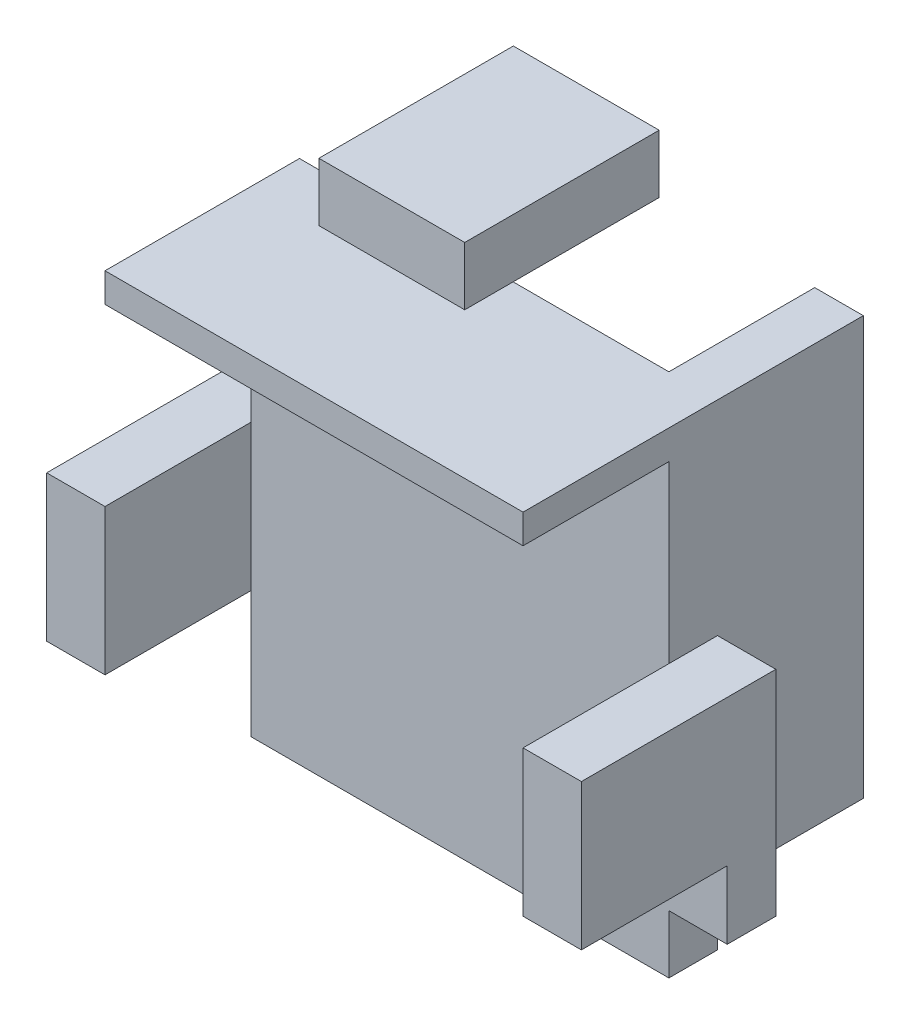
SolidWorks part; units mm, degrees
material "ABS"
ref_plane "前视基准面" through (0, 0, 0) normal (0, 0, 1) x (1, 0, 0)
ref_plane "上视基准面" through (0, 0, 0) normal (0, 1, 0) x (1, 0, 0)
ref_plane "右视基准面" through (0, 0, 0) normal (1, 0, 0) x (0, 0, -1)
sketch "草图1" plane through (0, 0, 0) normal (0, 0, 1) x (1, 0, 0)
  line L0 (-50.797, 9.0326) -> (-50.797, 3.0326)
  line L1 (-77.797, 31.0326) -> (-71.797, 31.0326)
  line L2 (-77.797, 31.0326) -> (-77.797, 9.0326)
  line L3 (-77.797, 9.0326) -> (-50.797, 9.0326)
  line L4 (-22.797, 31.0326) -> (-22.797, 9.0326)
  line L5 (-50.797, 58.0326) -> (-28.797, 58.0326)
  line L6 (-50.797, 58.0326) -> (-50.797, 52.0326)
  line L7 (-50.797, 3.0326) -> (-28.797, 3.0326)
  line L8 (-28.797, 58.0326) -> (-28.797, 31.0326)
  line L9 (-28.797, 9.0326) -> (-28.797, 3.0326)
  line L10 (-28.797, 9.0326) -> (-22.797, 9.0326)
  line L11 (-28.797, 31.0326) -> (-22.797, 31.0326)
  line L12 (-50.797, 49.0326) -> (-50.797, 31.0326)
  line L13 (-50.797, 9.0326) -> (-35.797, 9.0326)
  line L14 (-50.797, 9.0326) -> (-50.797, 3.0326)
  line L15 (-50.797, 3.0326) -> (-35.797, 3.0326)
  line L16 (-35.797, 9.0326) -> (-35.797, 3.0326)
  line L17 (-50.797, 52.0326) -> (-35.797, 52.0326)
  line L18 (-50.797, 52.0326) -> (-50.797, 58.0326)
  line L19 (-50.797, 58.0326) -> (-35.797, 58.0326)
  line L20 (-35.797, 52.0326) -> (-35.797, 58.0326)
  line L21 (-28.797, 31.0326) -> (-22.797, 31.0326)
  line L22 (-28.797, 31.0326) -> (-28.797, 16.0326)
  line L23 (-28.797, 16.0326) -> (-22.797, 16.0326)
  line L24 (-22.797, 31.0326) -> (-22.797, 16.0326)
  line L25 (-77.797, 31.0326) -> (-71.797, 31.0326)
  line L26 (-77.797, 31.0326) -> (-77.797, 16.0326)
  line L27 (-77.797, 16.0326) -> (-71.797, 16.0326)
  line L28 (-71.797, 31.0326) -> (-71.797, 16.0326)
  line L29 (-68.797, 9.0326) -> (-71.797, 9.0326)
  line L30 (-68.797, 9.0326) -> (-68.797, 49.0326)
  line L31 (-68.797, 49.0326) -> (-71.797, 49.0326)
  line L32 (-71.797, 9.0326) -> (-71.797, 49.0326)
  line L33 (-28.797, 49.0326) -> (-71.797, 49.0326)
  line L34 (-28.797, 49.0326) -> (-28.797, 52.0326)
  line L35 (-28.797, 52.0326) -> (-71.797, 52.0326)
  line L36 (-71.797, 49.0326) -> (-71.797, 52.0326)
  line L37 (-68.797, 31.0326) -> (-50.797, 31.0326)
  dimension "D1" = 55
  dimension "D2" = 22
  dimension "D3" = 55
  dimension "D4" = 22
  dimension "D5" = 6
  dimension "D6" = 6
  dimension "D7" = 15
  dimension "D8" = 6
  dimension "D9" = 15
  dimension "D10" = 15
  dimension "D11" = 6
  dimension "D12" = 15
  dimension "D13" = 3
  dimension "D14" = 40
extrude "拉伸-薄壁3" add sketch "草图1" along normal blind 15 thin contours L11 thin type one direction wall 15
extrude "凸台-拉伸3" add sketch "草图1<7>" along normal blind 15 separate body contours L28 L1 L2 L27 region at (-74.797, 23.5326, 0)
sketch "草图1<7>" plane through (0, 0, 0) normal (0, 0, 1) x (1, 0, 0) same geometry as "草图1"
extrude "凸台-拉伸4" add sketch "草图1<8>" along normal blind 15 separate body contours L36 L31 L33 L8 L35 L17 region at (-50.297, 50.5326, 0)
sketch "草图1<8>" plane through (0, 0, 0) normal (0, 0, 1) x (1, 0, 0) same geometry as "草图1"
extrude "凸台-拉伸5" add sketch "草图1<11>" against normal blind 5 contours L37 L30 L3 L13 L16 L7 L9 L10 L4 L23 L22 L8 L33 L12 | L30 L37 L12 L33 | L22 L23 L4 L11 | L28 L1 L2 L27 | L32 L3 L30 L31 L28 | L36 L31 L33 L8 L35 L17 | L17 L20 L5 L6 | L35 L8 L5 L20 | L16 L13 L0 L7 region at (-43.297, 6.0326, 0) region at (-44.9565, 25.1922, 0) region at (-70.297, 29.0326, 0) region at (-59.797, 40.0326, 0) region at (-74.797, 23.5326, 0) region at (-50.297, 50.5326, 0) region at (-25.797, 23.5326, 0) region at (-43.297, 55.0326, 0) region at (-32.297, 55.0326, 0)
sketch "草图1<11>" plane through (0, 0, 0) normal (0, 0, 1) x (1, 0, 0) same geometry as "草图1"
extrude "凸台-拉伸10" add sketch "草图1<13>" against normal blind 20 contours L32 L29 L30 L31
sketch "草图1<13>" plane through (0, 0, 0) normal (0, 0, 1) x (1, 0, 0) same geometry as "草图1"
sketch "草图3" plane through (0, 0, -5) normal (0, 0, -1) x (-1, 0, 0)
  line L0 (50.797, 58.0326) -> (28.797, 58.0326) construction
  line L1 (35.9279, 58.0326) -> (50.797, 58.0326)
  line L2 (35.9279, 58.0326) -> (35.9279, 52.0326)
  line L3 (35.9279, 52.0326) -> (50.797, 52.0326)
  line L4 (50.797, 58.0326) -> (50.797, 52.0326)
  line L5 (50.797, 3.0326) -> (28.797, 3.0326) construction
  line L6 (50.797, 9.0326) -> (35.9279, 9.0326)
  line L7 (50.797, 9.0326) -> (50.797, 3.0326)
  line L8 (50.797, 3.0326) -> (35.9279, 3.0326)
  line L9 (35.9279, 9.0326) -> (35.9279, 3.0326)
extrude "凸台-拉伸15" add sketch "草图3" along normal blind 15
sketch "草图4" plane through (0, 0, -5) normal (0, 0, -1) x (-1, 0, 0)
  line L2 (50.797, 52.0326) -> (28.797, 52.0326)
  line L3 (50.797, 52.0326) -> (50.797, 58.0326)
  line L4 (50.797, 58.0326) -> (28.797, 58.0326)
  line L5 (28.797, 52.0326) -> (28.797, 58.0326)
  line L6 (71.797, 52.0326) -> (64.797, 52.0326)
  line L7 (71.797, 52.0326) -> (71.797, 58.0326)
  line L8 (71.797, 58.0326) -> (64.797, 58.0326)
  line L9 (64.797, 52.0326) -> (64.797, 58.0326)
  dimension "D1" = 6
  dimension "D2" = 7
extrude "切除-拉伸2" cut sketch "草图4" against normal through all
sketch "草图8" plane through (0, 0, -20) normal (0, 0, -1) x (-1, 0, 0)
  line L0 (50.797, 58.0326) -> (35.9279, 58.0326) construction
  line L1 (35.9279, 58.0326) -> (50.797, 58.0326)
  line L2 (35.9279, 58.0326) -> (35.9279, 52.0326)
  line L3 (35.9279, 52.0326) -> (50.797, 52.0326)
  line L4 (50.797, 58.0326) -> (50.797, 52.0326)
  line L5 (35.9279, 58.0326) -> (35.9279, 52.0326) construction
extrude "切除-拉伸3" cut sketch "草图8" against normal through all
sketch "草图10" plane through (0, 0, 0) normal (0, 0, 1) x (1, 0, 0)
  line L0 (-71.797, 49.0326) -> (-71.797, 52.0326) construction
  line L1 (-64.797, 52.0532) -> (-49.797, 52.0532)
  line L2 (-64.797, 52.0532) -> (-64.797, 58.0532)
  line L3 (-64.797, 58.0532) -> (-49.797, 58.0532)
  line L4 (-49.797, 52.0532) -> (-49.797, 58.0532)
  dimension "D1" = 15
  dimension "D2" = 6
  dimension "D3" = 7
extrude "凸台-拉伸16" add sketch "草图10" against normal up to vertex (20 mm away) separate body up to point (-35.9279, 3.0326, -20)
sketch "草图15" plane through (0, 0, 0) normal (0, 0, 1) x (1, 0, 0)
  line L1 (-71.797, 9.0326) -> (-64.797, 9.0326)
  line L2 (-71.797, 9.0326) -> (-71.797, 3.0326)
  line L3 (-71.797, 3.0326) -> (-64.797, 3.0326)
  line L4 (-64.797, 9.0326) -> (-64.797, 3.0326)
  line L5 (-64.797, 9.0326) -> (-49.797, 9.0326)
  line L6 (-64.797, 9.0326) -> (-64.797, 3.0326)
  line L7 (-64.797, 3.0326) -> (-49.797, 3.0326)
  line L8 (-49.797, 9.0326) -> (-49.797, 3.0326)
  dimension "D1" = 6
  dimension "D2" = 7
  dimension "D3" = 15
extrude "凸台-拉伸17" add sketch "草图15" against normal blind 5 contours L3 L4 L1 L2
sketch "草图16" plane through (0, 0, 0) normal (0, 0, 1) x (1, 0, 0)
  line L0 (-28.797, 9.0326) -> (-22.797, 9.0326) construction
  line L1 (-64.797, 3.0326) -> (-49.797, 3.0326)
  line L2 (-64.797, 3.0326) -> (-64.797, 9.0326)
  line L3 (-64.797, 9.0326) -> (-49.797, 9.0326)
  line L4 (-49.797, 3.0326) -> (-49.797, 9.0326)
  dimension "D1" = 15
extrude "凸台-拉伸18" add sketch "草图16" against normal up to vertex (20 mm away) up to point (-49.797, 52.0532, -20)
sketch "草图17" plane through (0, 0, -5) normal (0, 0, -1) x (-1, 0, 0)
  line L1 (68.797, 49.0326) -> (71.797, 49.0326)
  line L2 (68.797, 49.0326) -> (68.797, 9.0326)
  line L3 (68.797, 9.0326) -> (71.797, 9.0326)
  line L4 (71.797, 49.0326) -> (71.797, 9.0326)
extrude "切除-拉伸5" cut sketch "草图17" along normal through all contours L2 L3 L4 L1
sketch "草图18" plane through (0, 0, -5) normal (0, 0, -1) x (-1, 0, 0)
  line L0 (28.797, 9.0326) -> (22.797, 9.0326) construction
  line L1 (28.797, 52.0326) -> (33.797, 52.0326)
  line L2 (28.797, 52.0326) -> (28.797, 9.0326)
  line L3 (28.797, 9.0326) -> (33.797, 9.0326)
  line L4 (33.797, 52.0326) -> (33.797, 9.0326)
  dimension "D1" = 5
extrude "凸台-拉伸19" add sketch "草图18" along normal up to vertex (15 mm away) up to point (-49.797, 52.0532, -20)
